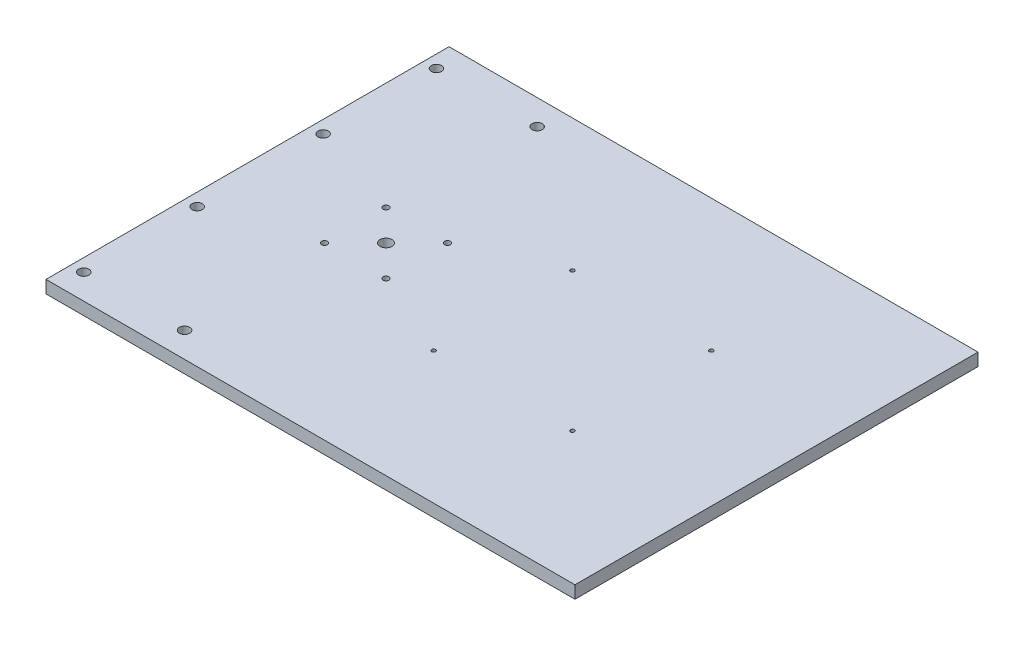
SolidWorks part; units mm, degrees
ref_plane "Front Plane" through (0, 0, 0) normal (0, 0, 1) x (1, 0, 0)
ref_plane "Top Plane" through (0, 0, 0) normal (0, 1, 0) x (1, 0, 0)
ref_plane "Right Plane" through (0, 0, 0) normal (1, 0, 0) x (0, 0, -1)
sketch "Sketch1" plane through (0, 0, 0) normal (0, 1, 0) x (1, 0, 0)
  line L1 (-133.35, -101.6) -> (133.35, -101.6)
  line L2 (-133.35, -101.6) -> (-133.35, 101.6)
  line L3 (-133.35, 101.6) -> (133.35, 101.6)
  line L4 (133.35, -101.6) -> (133.35, 101.6)
  line L5 (-133.35, -101.6) -> (133.35, 101.6) construction
  line L6 (-133.35, 101.6) -> (133.35, -101.6) construction
  point P0 (0, 0)
  dimension "D1" = 203.2
  dimension "D2" = 266.7
extrude "Boss-Extrude1" add sketch "Sketch1" along normal blind 6.35
sketch "Sketch2" plane through (0, 0, 0) normal (0, 1, 0) x (1, 0, 0)
  line L0 (-193.2668, 0) -> (192.9727, 0) construction
sketch "Sketch3" plane through (0, 6.35, 0) normal (0, 1, 0) x (1, 0, 0)
  circle A1 centre (-127, -31.75) radius 2.6
  circle A2 centre (-127, -31.75) radius 2.6
  circle A3 centre (-76.2, -88.9) radius 2.6
  circle A4 centre (-76.2, -88.9) radius 2.6
  circle A5 centre (-127, -88.9) radius 2.6
  circle A6 centre (-127, -88.9) radius 2.6
  dimension "D1" = 0
  dimension "D2" = 0
  dimension "D3" = 0
sketch "Sketch5" plane through (0, 6.35, 0) normal (0, 1, 0) x (1, 0, 0)
  circle A0 centre (-48.024, 15.5) radius 1.5 construction
  circle A1 centre (-48.024, -15.5) radius 1.5 construction
  circle A2 centre (-79.024, 15.5) radius 1.5 construction
  circle A3 centre (-79.024, -15.5) radius 1.5 construction
  circle A4 centre (-63.524, 0) radius 2.5 construction
  circle A5 centre (-48.024, 15.5) radius 1.5
  circle A6 centre (-48.024, -15.5) radius 1.5
  circle A7 centre (-79.024, 15.5) radius 1.5
  circle A8 centre (-79.024, -15.5) radius 1.5
  circle A9 centre (-63.524, 0) radius 2.5 construction
  circle A10 centre (-63.524, 0) radius 3.008
  dimension "D1" = 6.016
sketch "Sketch7" plane through (0, 6.35, 0) normal (0, 1, 0) x (1, 0, 0)
  circle A0 centre (65.4818, -35.0018) radius 1 construction
  circle A1 centre (-4.5218, -35.0018) radius 1 construction
  circle A2 centre (65.4818, -35.0018) radius 1
  circle A3 centre (-4.5218, -35.0018) radius 1
  circle A4 centre (-4.5218, 35.0018) radius 1 construction
  circle A5 centre (65.4818, 35.0018) radius 1 construction
  circle A6 centre (-4.5218, 35.0018) radius 1
  circle A7 centre (65.4818, 35.0018) radius 1
extrude "Cut-Extrude1" cut sketch "Sketch3" against normal through all
mirror "Mirror1" about plane through (0, 0, 0) normal (0, 0, 1) of "Cut-Extrude1"
extrude "Cut-Extrude2" cut sketch "Sketch5" against normal through all
extrude "Cut-Extrude3" cut sketch "Sketch7" against normal through all
equation "\"tightTol\"= 0.005in"
equation "\"normTol\"= 0.01in"
equation "\"looseTol\"= 0.02in"
equation "\"D1@Sketch5\"=5mm+2*\"looseTol\""
